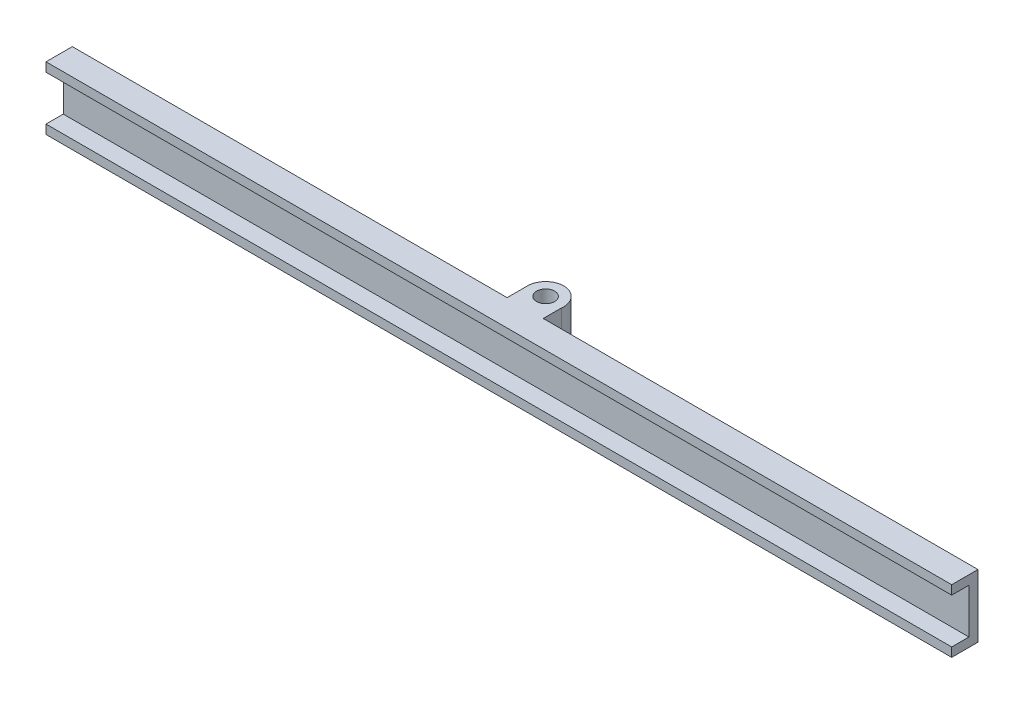
SolidWorks part; units mm, degrees
material "PLA"
ref_plane "Front Plane" through (0, 0, 0) normal (1, 0, 0) x (0, 1, 0)
ref_plane "Top Plane" through (0, 0, 0) normal (0, 0, 1) x (0, 1, 0)
ref_plane "Right Plane" through (0, 0, 0) normal (0, 1, 0) x (-1, 0, 0)
sketch "Sketch1" plane through (0, 0, 0) normal (1, 0, 0) x (0, 1, 0)
  line L16 (0, 4.7625) -> (-2.5, 4.7625)
  line L17 (0, 0) -> (12.3825, 0)
  line L18 (0, 0) -> (0, 4.7625)
  line L19 (0, 4.7625) -> (12.3825, 4.7625) construction
  line L20 (12.3825, 0) -> (12.3825, 4.7625)
  line L21 (-2.5, 4.7625) -> (-2.5, -2.5)
  line L22 (-2.5, -2.5) -> (14.8825, -2.5)
  line L23 (14.8825, -2.5) -> (14.8825, 4.7625)
  line L24 (12.3825, 4.7625) -> (14.8825, 4.7625)
  dimension "D1" = 4.7625
  dimension "D2" = 12.3825
  dimension "D3" = 2.5
  dimension "D4" = 2.5
extrude "Boss-Extrude1" add sketch "Sketch1" along normal blind 250
sketch "Sketch3" plane through (0, -2.5, 0) normal (0, -1, 0) x (1, 0, 0)
  line L0 (120.0194, -2.5) -> (129.9806, -2.5)
  line L1 (250, -2.5) -> (0, -2.5) construction
  line L2 (129.9806, -2.5) -> (129.9806, -7.5)
  line L3 (120.0194, -2.5) -> (120.0194, -8.1217)
  line L4 (0, 4.7625) -> (0, -2.5) construction
  arc A0 (120.0194, -8.1217) -> (129.9806, -7.5) centre (125.0194, -8.1217) ccw
  circle A1 centre (125.0194, -8.1217) radius 2.5
  point P5 (125, -2.5)
  dimension "D3" = 5
  dimension "D4" = 125
extrude "Boss-Extrude2" add sketch "Sketch3" against normal up to surface (17.3825 mm away) up to face at (125, 14.8825, 1.1313)
sketch "Sketch6" plane through (0, -2.5, 0) normal (0, -1, 0) x (1, 0, 0)
  line L0 (120.0194, -2.5) -> (0, -2.5) construction
  line L1 (117.5385, -2.5) -> (131.3691, -2.5)
  line L2 (117.5385, -2.5) -> (117.5385, -13.6365)
  line L3 (117.5385, -13.6365) -> (131.3691, -13.6365)
  line L4 (131.3691, -2.5) -> (131.3691, -13.6365)
extrude "Cut-Extrude2" [suppressed] cut sketch "Sketch6" against normal blind 5
sketch "Sketch7" plane through (0, 14.8825, 0) normal (0, 1, 0) x (-1, 0, 0)
  line L0 (-250, -2.5) -> (-129.9806, -2.5) construction
  line L1 (-136.5723, -2.5) -> (-116.3235, -2.5)
  line L2 (-136.5723, -2.5) -> (-136.5723, -14.7915)
  line L3 (-136.5723, -14.7915) -> (-116.3235, -14.7915)
  line L4 (-116.3235, -2.5) -> (-116.3235, -14.7915)
extrude "Cut-Extrude3" [suppressed] cut sketch "Sketch7" against normal blind 5
equation "\"D1@Sketch1\"=\"ball_diameter\" * 0.25"
equation "\"D2@Sketch1\"=\"ball_diameter\" * 0.65"
equation "\"D3@Sketch1\"=\"wall_thickness\""
equation "\"D4@Sketch1\"=\"wall_thickness\""
equation "\"D1@Boss-Extrude1\"=\"track_length\""
equation "\"D2@Sketch3\"= \"axle\""
equation "\"ball_diameter\"= 0.75in"
equation "\"wall_thickness\" = 0.25cm"
equation "\"track_length\" = 25cm"
equation "\"axle\" = 5mm"
equation "\"D3@Sketch3\"=\"axle\" * 1"
equation "\"D4@Sketch3\"=\"track_length\" / 2"
equation "\"pillar_width\" = 2.75cm"
